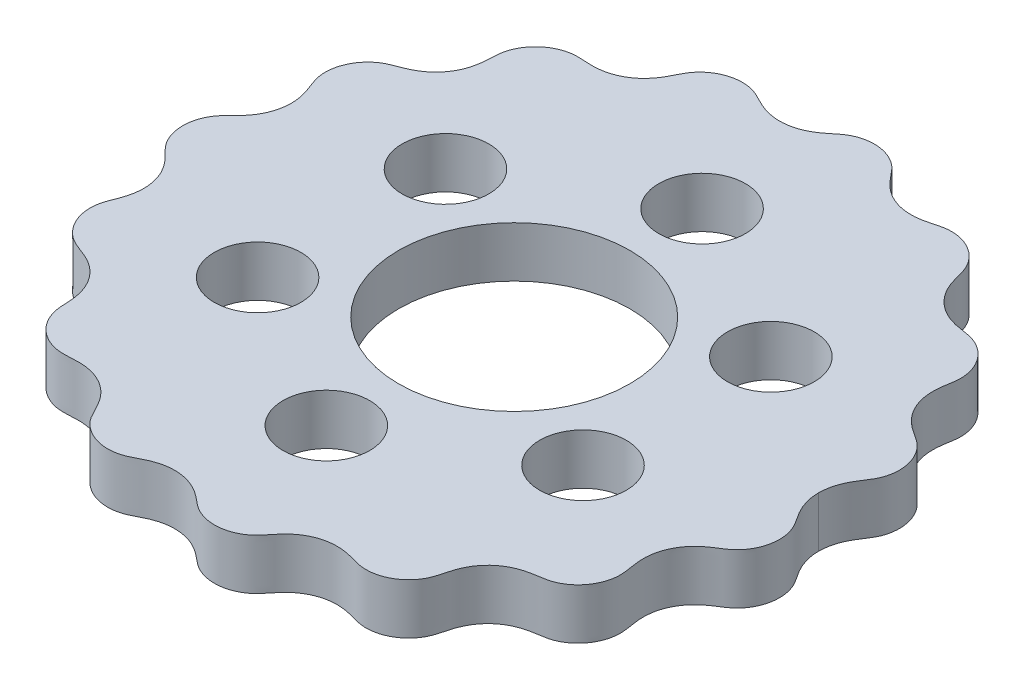
SolidWorks part; units mm, degrees
ref_plane "Front Plane" through (0, 0, 0) normal (0, 0, 1) x (1, 0, 0)
ref_plane "Top Plane" through (0, 0, 0) normal (0, 1, 0) x (1, 0, 0)
ref_plane "Right Plane" through (0, 0, 0) normal (1, 0, 0) x (0, 0, -1)
sketch "Sketch1" plane through (0, 0, 0) normal (0, 1, 0) x (1, 0, 0)
  spline S0 degree 4 poles (44.0747, 11.4987) (44.2543, 11.2167) (44.5698, 10.6242) (44.9021, 9.6808) (45.0642, 8.3642) (44.9446, 7.1282) (44.593, 6.0249) (44.1211, 5.1947) (43.695, 4.5754) (43.3564, 4.0472) (43.0998, 3.6163) (42.8821, 3.198) (42.6994, 2.7973) (42.5503, 2.4153) (42.4301, 2.0557) (42.3415, 1.7357) (42.2778, 1.4587) (42.224, 1.1791) (42.1875, 0.9457) (42.1595, 0.7089) (42.1421, 0.4978) (42.1336, 0.3578) (42.1278, 0.2085) (42.1243, 0.037) (42.1247, -0.0678) (42.1293, -0.2634) (42.1379, -0.4367) (42.15, -0.5999) (42.1691, -0.7936) (42.1974, -1.0101) (42.2414, -1.2799) (42.3074, -1.6012) (42.4037, -1.9716) (42.5387, -2.3877) (42.6983, -2.7948) (42.8796, -3.1931) (43.1366, -3.6835) (43.482, -4.2594) (43.9287, -4.9065) (44.4091, -5.6745) (44.8007, -6.6105) (45.0295, -7.7093) (45.0295, -8.9484) (44.7352, -10.2696) (44.1902, -11.4212) (43.4619, -12.3657) (42.6206, -13.0778) (41.7593, -13.602) (40.7824, -14.2408) (39.77, -15.1062) (38.838, -16.2841) (38.1405, -17.7977) (37.8498, -19.2831) (37.8586, -20.6377) (38.0279, -21.8199) (38.2279, -22.8394) (38.2788, -23.9779) (38.0615, -25.1966) (37.5489, -26.4121) (36.7247, -27.5436) (35.7476, -28.3911) (34.706, -28.96) (33.6586, -29.2738) (32.6702, -29.405) (31.5286, -29.5836) (30.2595, -29.9481) (28.9262, -30.6268) (27.659, -31.7106) (26.7717, -32.9447) (26.2118, -34.1914) (25.9145, -35.2243) (25.7304, -35.9895) (25.5039, -36.7438) (25.1586, -37.555) (24.5413, -38.4785) (23.5696, -39.3957) (22.3328, -40.1097) (21.0527, -40.4927) (19.9443, -40.5655) (19.0691, -40.4589) (18.3026, -40.2779) (17.5479, -40.0547) (16.5047, -39.7958) (15.1451, -39.6573) (13.6327, -39.8087) (12.0605, -40.3642) (10.8061, -41.1795) (9.8558, -42.0964) (9.1304, -42.9957) (8.5226, -43.7861) (7.7271, -44.5363) (6.7136, -45.1539) (5.4911, -45.5763) (4.0991, -45.7244) (2.7902, -45.5605) (1.6261, -45.1394) (0.6656, -44.526) (-0.1173, -43.8431) (-1.0565, -43.1053) (-2.2252, -42.4205) (-3.657, -41.9295) (-5.3166, -41.7767) (-6.8026, -41.9949) (-8.0583, -42.439) (-9.1, -42.9656) (-9.9846, -43.4494) (-11.0219, -43.8219) (-12.2041, -43.9805) (-13.4901, -43.8751) (-14.8122, -43.455) (-15.9301, -42.7928) (-16.8127, -41.9651) (-17.4446, -41.0507) (-17.8788, -40.1387) (-18.4163, -39.084) (-19.1877, -37.9587) (-20.2985, -36.882) (-21.7915, -36.02) (-23.2794, -35.5964) (-24.6396, -35.491) (-25.8217, -35.5529) (-26.8286, -35.6328) (-27.9365, -35.5428) (-29.0946, -35.1922) (-30.227, -34.5552) (-31.2519, -33.6204) (-31.9862, -32.5593) (-32.4399, -31.4562) (-32.636, -30.3717) (-32.6594, -29.3636) (-32.7241, -28.1982) (-32.9674, -26.8887) (-33.5214, -25.4926) (-34.4835, -24.1318) (-35.6246, -23.1374) (-36.8021, -22.4676) (-37.9106, -22.0232) (-38.8934, -21.6866) (-39.9049, -21.1614) (-40.8517, -20.3639) (-41.648, -19.3123) (-42.2158, -18.0327) (-42.4612, -16.7628) (-42.4331, -15.5762) (-42.1811, -14.5123) (-41.8006, -13.5907) (-41.3845, -12.5128) (-41.0655, -11.2314) (-40.9867, -9.7374) (-41.2916, -8.0981) (-41.8623, -6.8333) (-42.485, -5.9251) (-43.0125, -5.3085) (-43.3736, -4.9275) (-43.7476, -4.5595) (-44.1231, -4.193) (-44.4829, -3.8105) (-44.8105, -3.3997) (-45.0744, -2.9955) (-45.2825, -2.6081) (-45.444, -2.2456) (-45.5676, -1.9138) (-45.6577, -1.6174) (-45.7221, -1.3598) (-45.7672, -1.1433) (-45.7981, -0.9691) (-45.8239, -0.7941) (-45.8419, -0.6396) (-45.8542, -0.5087) (-45.8622, -0.3996) (-45.8674, -0.31) (-45.8722, -0.1929) (-45.8754, -0.0484) (-45.8754, 0.057) (-45.8707, 0.2539) (-45.8614, 0.4217) (-45.8475, 0.5867) (-45.8289, 0.7543) (-45.8057, 0.9209) (-45.7778, 1.0866) (-45.7208, 1.3751) (-45.6162, 1.7824) (-45.4517, 2.2512) (-45.2056, 2.7679) (-44.9364, 3.2145) (-44.6596, 3.5954) (-44.3529, 3.9526) (-44.0247, 4.2897) (-43.6878, 4.6178) (-43.3537, 4.9489) (-43.036, 5.2844) (-42.7388, 5.6275) (-42.4647, 5.9787) (-42.2147, 6.3375) (-41.9285, 6.8032) (-41.6301, 7.388) (-41.2988, 8.2445) (-41.0869, 9.2182) (-41.0245, 10.1783) (-41.079, 10.9169) (-41.1306, 11.2832) (-41.1623, 11.4653) knots 0 0 0 0 0 0.00752 0.015039 0.022311 0.029582 0.03522 0.040858 0.043677 0.046496 0.049315 0.052134 0.054265 0.056396 0.058526 0.060657 0.061722 0.062788 0.064918 0.065984 0.067049 0.067582 0.068115 0.06918 0.070492 0.071149 0.071805 0.073033 0.074262 0.07549 0.076719 0.079176 0.081633 0.084089 0.086546 0.089003 0.09146 0.096539 0.101618 0.106697 0.111776 0.11923 0.126684 0.134323 0.141963 0.147625 0.153288 0.15895 0.164612 0.173852 0.183092 0.192408 0.201724 0.207559 0.213395 0.219231 0.225067 0.233024 0.240981 0.24862 0.25626 0.261858 0.267455 0.273053 0.278651 0.287828 0.297005 0.30639 0.315776 0.321674 0.327572 0.330521 0.33347 0.339368 0.347323 0.355277 0.363232 0.371186 0.377084 0.380033 0.382982 0.38888 0.394778 0.404164 0.413549 0.422726 0.431904 0.437501 0.443099 0.448697 0.454294 0.461934 0.469574 0.477531 0.485487 0.491323 0.497159 0.502995 0.508831 0.518146 0.527462 0.536702 0.545942 0.551604 0.557267 0.562929 0.568591 0.576231 0.58387 0.591691 0.599511 0.605182 0.610853 0.616525 0.622196 0.631785 0.641374 0.650964 0.660553 0.666224 0.671895 0.677566 0.683238 0.691058 0.698878 0.706518 0.714157 0.71982 0.725482 0.731145 0.736807 0.746047 0.755287 0.764602 0.773918 0.779754 0.78559 0.791426 0.797261 0.805218 0.813175 0.820815 0.828454 0.834052 0.83965 0.845248 0.850845 0.860022 0.869199 0.878585 0.887971 0.89092 0.893869 0.896818 0.899767 0.902716 0.905665 0.908614 0.911563 0.913551 0.91554 0.917528 0.919517 0.920511 0.921506 0.9225 0.923494 0.924489 0.924986 0.925483 0.92598 0.926477 0.927472 0.928416 0.929361 0.930305 0.931249 0.932194 0.933138 0.934083 0.935027 0.938805 0.942583 0.945226 0.947869 0.950513 0.953156 0.955799 0.958442 0.961086 0.963729 0.966185 0.968641 0.971097 0.973554 0.978466 0.983378 0.991689 0.995845 1 1 1 1 1 construction
  spline S1 degree 4 poles (42.125, 0) (42.125, -0.0501) (42.126, -0.1243) (42.1293, -0.2634) (42.1379, -0.4367) (42.15, -0.5999) (42.1691, -0.7936) (42.1974, -1.0101) (42.2414, -1.2799) (42.3074, -1.6012) (42.4037, -1.9716) (42.5387, -2.3877) (42.6983, -2.7948) (42.8796, -3.1931) (43.1366, -3.6835) (43.482, -4.2594) (43.9287, -4.9065) (44.4091, -5.6745) (44.8007, -6.6105) (45.0295, -7.7093) (45.0295, -8.9484) (44.7352, -10.2696) (44.1902, -11.4212) (43.4619, -12.3657) (42.6206, -13.0778) (41.7593, -13.602) (40.7824, -14.2408) (39.77, -15.1062) (38.838, -16.2841) (38.1405, -17.7977) (37.8498, -19.2831) (37.8586, -20.6377) (38.0279, -21.8199) (38.2279, -22.8394) (38.2788, -23.9779) (38.0615, -25.1966) (37.5489, -26.4121) (36.7247, -27.5436) (35.7476, -28.3911) (34.706, -28.96) (33.6586, -29.2738) (32.6702, -29.405) (31.5286, -29.5836) (30.2595, -29.9481) (28.9262, -30.6268) (27.659, -31.7106) (26.7717, -32.9447) (26.2118, -34.1914) (25.9145, -35.2243) (25.7304, -35.9895) (25.5039, -36.7438) (25.1586, -37.555) (24.5413, -38.4785) (23.5696, -39.3957) (22.3328, -40.1097) (21.0527, -40.4927) (19.9443, -40.5655) (19.0691, -40.4589) (18.3026, -40.2779) (17.5479, -40.0547) (16.5047, -39.7958) (15.1451, -39.6573) (13.6327, -39.8087) (12.0605, -40.3642) (10.8061, -41.1795) (9.8558, -42.0964) (9.1304, -42.9957) (8.5226, -43.7861) (7.7271, -44.5363) (6.7136, -45.1539) (5.4911, -45.5763) (4.0991, -45.7244) (2.7902, -45.5605) (1.6261, -45.1394) (0.6656, -44.526) (-0.1173, -43.8431) (-1.0565, -43.1053) (-2.2252, -42.4205) (-3.657, -41.9295) (-5.3166, -41.7767) (-6.8026, -41.9949) (-8.0583, -42.439) (-9.1, -42.9656) (-9.9846, -43.4494) (-11.0219, -43.8219) (-12.2041, -43.9805) (-13.4901, -43.8751) (-14.8122, -43.455) (-15.9301, -42.7928) (-16.8127, -41.9651) (-17.4446, -41.0507) (-17.8788, -40.1387) (-18.4163, -39.084) (-19.1877, -37.9587) (-20.2985, -36.882) (-21.7915, -36.02) (-23.2794, -35.5964) (-24.6396, -35.491) (-25.8217, -35.5529) (-26.8286, -35.6328) (-27.9365, -35.5428) (-29.0946, -35.1922) (-30.227, -34.5552) (-31.2519, -33.6204) (-31.9862, -32.5593) (-32.4399, -31.4562) (-32.636, -30.3717) (-32.6594, -29.3636) (-32.7241, -28.1982) (-32.9674, -26.8887) (-33.5214, -25.4926) (-34.4835, -24.1318) (-35.6246, -23.1374) (-36.8021, -22.4676) (-37.9106, -22.0232) (-38.8934, -21.6866) (-39.9049, -21.1614) (-40.8517, -20.3639) (-41.648, -19.3123) (-42.2158, -18.0327) (-42.4612, -16.7628) (-42.4331, -15.5762) (-42.1811, -14.5123) (-41.8006, -13.5907) (-41.3845, -12.5128) (-41.0655, -11.2314) (-40.9867, -9.7374) (-41.2916, -8.0981) (-41.8623, -6.8333) (-42.485, -5.9251) (-43.0125, -5.3085) (-43.3736, -4.9275) (-43.7476, -4.5595) (-44.1231, -4.193) (-44.4829, -3.8105) (-44.8105, -3.3997) (-45.0744, -2.9955) (-45.2825, -2.6081) (-45.444, -2.2456) (-45.5676, -1.9138) (-45.6577, -1.6174) (-45.7221, -1.3598) (-45.7672, -1.1433) (-45.7981, -0.9691) (-45.8239, -0.7941) (-45.8419, -0.6396) (-45.8542, -0.5087) (-45.8622, -0.3996) (-45.8674, -0.31) (-45.8722, -0.1929) (-45.8744, -0.0949) (-45.875, -0.038) (-45.875, 0) knots 0.06918 0.06918 0.06918 0.06918 0.06918 0.070492 0.071149 0.071805 0.073033 0.074262 0.07549 0.076719 0.079176 0.081633 0.084089 0.086546 0.089003 0.09146 0.096539 0.101618 0.106697 0.111776 0.11923 0.126684 0.134323 0.141963 0.147625 0.153288 0.15895 0.164612 0.173852 0.183092 0.192408 0.201724 0.207559 0.213395 0.219231 0.225067 0.233024 0.240981 0.24862 0.25626 0.261858 0.267455 0.273053 0.278651 0.287828 0.297005 0.30639 0.315776 0.321674 0.327572 0.330521 0.33347 0.339368 0.347323 0.355277 0.363232 0.371186 0.377084 0.380033 0.382982 0.38888 0.394778 0.404164 0.413549 0.422726 0.431904 0.437501 0.443099 0.448697 0.454294 0.461934 0.469574 0.477531 0.485487 0.491323 0.497159 0.502995 0.508831 0.518146 0.527462 0.536702 0.545942 0.551604 0.557267 0.562929 0.568591 0.576231 0.58387 0.591691 0.599511 0.605182 0.610853 0.616525 0.622196 0.631785 0.641374 0.650964 0.660553 0.666224 0.671895 0.677566 0.683238 0.691058 0.698878 0.706518 0.714157 0.71982 0.725482 0.731145 0.736807 0.746047 0.755287 0.764602 0.773918 0.779754 0.78559 0.791426 0.797261 0.805218 0.813175 0.820815 0.828454 0.834052 0.83965 0.845248 0.850845 0.860022 0.869199 0.878585 0.887971 0.89092 0.893869 0.896818 0.899767 0.902716 0.905665 0.908614 0.911563 0.913551 0.91554 0.917528 0.919517 0.920511 0.921506 0.9225 0.923494 0.924489 0.924986 0.925483 0.92598 0.926477 0.927472 0.927472 0.927472 0.927472 0.927472
  spline S2 degree 4 poles (42.125, 0) (42.125, 0.0501) (42.126, 0.1243) (42.1293, 0.2634) (42.1379, 0.4367) (42.15, 0.5999) (42.1691, 0.7936) (42.1974, 1.0101) (42.2414, 1.2799) (42.3074, 1.6012) (42.4037, 1.9716) (42.5387, 2.3877) (42.6983, 2.7948) (42.8796, 3.1931) (43.1366, 3.6835) (43.482, 4.2594) (43.9287, 4.9065) (44.4091, 5.6745) (44.8007, 6.6105) (45.0295, 7.7093) (45.0295, 8.9484) (44.7352, 10.2696) (44.1902, 11.4212) (43.4619, 12.3657) (42.6206, 13.0778) (41.7593, 13.602) (40.7824, 14.2408) (39.77, 15.1062) (38.838, 16.2841) (38.1405, 17.7977) (37.8498, 19.2831) (37.8586, 20.6377) (38.0279, 21.8199) (38.2279, 22.8394) (38.2788, 23.9779) (38.0615, 25.1966) (37.5489, 26.4121) (36.7247, 27.5436) (35.7476, 28.3911) (34.706, 28.96) (33.6586, 29.2738) (32.6702, 29.405) (31.5286, 29.5836) (30.2595, 29.9481) (28.9262, 30.6268) (27.659, 31.7106) (26.7717, 32.9447) (26.2118, 34.1914) (25.9145, 35.2243) (25.7304, 35.9895) (25.5039, 36.7438) (25.1586, 37.555) (24.5413, 38.4785) (23.5696, 39.3957) (22.3328, 40.1097) (21.0527, 40.4927) (19.9443, 40.5655) (19.0691, 40.4589) (18.3026, 40.2779) (17.5479, 40.0547) (16.5047, 39.7958) (15.1451, 39.6573) (13.6327, 39.8087) (12.0605, 40.3642) (10.8061, 41.1795) (9.8558, 42.0964) (9.1304, 42.9957) (8.5226, 43.7861) (7.7271, 44.5363) (6.7136, 45.1539) (5.4911, 45.5763) (4.0991, 45.7244) (2.7902, 45.5605) (1.6261, 45.1394) (0.6656, 44.526) (-0.1173, 43.8431) (-1.0565, 43.1053) (-2.2252, 42.4205) (-3.657, 41.9295) (-5.3166, 41.7767) (-6.8026, 41.9949) (-8.0583, 42.439) (-9.1, 42.9656) (-9.9846, 43.4494) (-11.0219, 43.8219) (-12.2041, 43.9805) (-13.4901, 43.8751) (-14.8122, 43.455) (-15.9301, 42.7928) (-16.8127, 41.9651) (-17.4446, 41.0507) (-17.8788, 40.1387) (-18.4163, 39.084) (-19.1877, 37.9587) (-20.2985, 36.882) (-21.7915, 36.02) (-23.2794, 35.5964) (-24.6396, 35.491) (-25.8217, 35.5529) (-26.8286, 35.6328) (-27.9365, 35.5428) (-29.0946, 35.1922) (-30.227, 34.5552) (-31.2519, 33.6204) (-31.9862, 32.5593) (-32.4399, 31.4562) (-32.636, 30.3717) (-32.6594, 29.3636) (-32.7241, 28.1982) (-32.9674, 26.8887) (-33.5214, 25.4926) (-34.4835, 24.1318) (-35.6246, 23.1374) (-36.8021, 22.4676) (-37.9106, 22.0232) (-38.8934, 21.6866) (-39.9049, 21.1614) (-40.8517, 20.3639) (-41.648, 19.3123) (-42.2158, 18.0327) (-42.4612, 16.7628) (-42.4331, 15.5762) (-42.1811, 14.5123) (-41.8006, 13.5907) (-41.3845, 12.5128) (-41.0655, 11.2314) (-40.9867, 9.7374) (-41.2916, 8.0981) (-41.8623, 6.8333) (-42.485, 5.9251) (-43.0125, 5.3085) (-43.3736, 4.9275) (-43.7476, 4.5595) (-44.1231, 4.193) (-44.4829, 3.8105) (-44.8105, 3.3997) (-45.0744, 2.9955) (-45.2825, 2.6081) (-45.444, 2.2456) (-45.5676, 1.9138) (-45.6577, 1.6174) (-45.7221, 1.3598) (-45.7672, 1.1433) (-45.7981, 0.9691) (-45.8239, 0.7941) (-45.8419, 0.6396) (-45.8542, 0.5087) (-45.8622, 0.3996) (-45.8674, 0.31) (-45.8722, 0.1929) (-45.8744, 0.0949) (-45.875, 0.038) (-45.875, 0) knots 0.06918 0.06918 0.06918 0.06918 0.06918 0.070492 0.071149 0.071805 0.073033 0.074262 0.07549 0.076719 0.079176 0.081633 0.084089 0.086546 0.089003 0.09146 0.096539 0.101618 0.106697 0.111776 0.11923 0.126684 0.134323 0.141963 0.147625 0.153288 0.15895 0.164612 0.173852 0.183092 0.192408 0.201724 0.207559 0.213395 0.219231 0.225067 0.233024 0.240981 0.24862 0.25626 0.261858 0.267455 0.273053 0.278651 0.287828 0.297005 0.30639 0.315776 0.321674 0.327572 0.330521 0.33347 0.339368 0.347323 0.355277 0.363232 0.371186 0.377084 0.380033 0.382982 0.38888 0.394778 0.404164 0.413549 0.422726 0.431904 0.437501 0.443099 0.448697 0.454294 0.461934 0.469574 0.477531 0.485487 0.491323 0.497159 0.502995 0.508831 0.518146 0.527462 0.536702 0.545942 0.551604 0.557267 0.562929 0.568591 0.576231 0.58387 0.591691 0.599511 0.605182 0.610853 0.616525 0.622196 0.631785 0.641374 0.650964 0.660553 0.666224 0.671895 0.677566 0.683238 0.691058 0.698878 0.706518 0.714157 0.71982 0.725482 0.731145 0.736807 0.746047 0.755287 0.764602 0.773918 0.779754 0.78559 0.791426 0.797261 0.805218 0.813175 0.820815 0.828454 0.834052 0.83965 0.845248 0.850845 0.860022 0.869199 0.878585 0.887971 0.89092 0.893869 0.896818 0.899767 0.902716 0.905665 0.908614 0.911563 0.913551 0.91554 0.917528 0.919517 0.920511 0.921506 0.9225 0.923494 0.924489 0.924986 0.925483 0.92598 0.926477 0.927472 0.927472 0.927472 0.927472 0.927472
extrude "Boss-Extrude2" add sketch "Sketch1" along normal blind 7
sketch "Sketch3" plane through (0, 7, 0) normal (0, 1, 0) x (1, 0, 0)
  circle A0 centre (0, 0) radius 16
  dimension "D1" = 32
extrude "Cut-Extrude1" cut sketch "Sketch3" against normal blind 7
sketch "Sketch4" plane through (0, 7, 0) normal (0, 1, 0) x (1, 0, 0)
  circle A0 centre (0, 26) radius 6
  circle A1 centre (22.5167, 13) radius 6
  circle A2 centre (22.5167, -13) radius 6
  circle A3 centre (0, -26) radius 6
  circle A4 centre (-22.5167, -13) radius 6
  circle A5 centre (-22.5167, 13) radius 6
  point P16 (0, 0)
  dimension "D1" = 12
  dimension "D2" = 26
  dimension "D3" = 6
extrude "Cut-Extrude2" cut sketch "Sketch4" against normal blind 15
